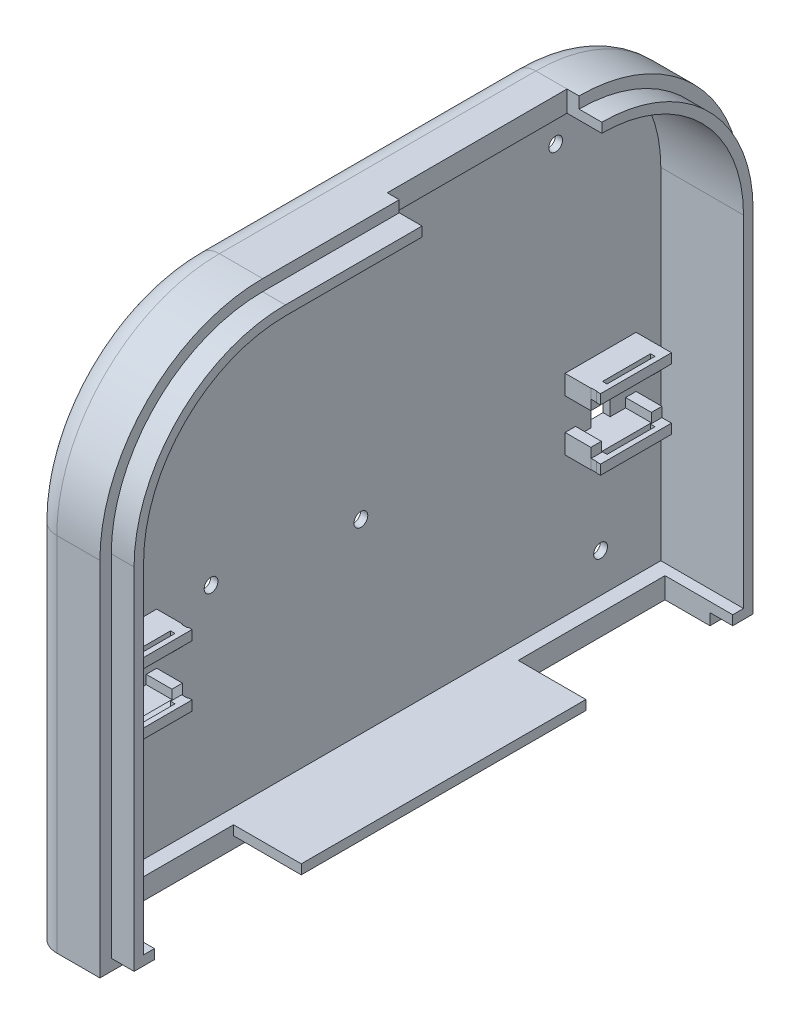
SolidWorks part; units mm, degrees
ref_plane "Front Plane" through (0, 0, 0) normal (0, 0, 1) x (1, 0, 0)
ref_plane "Top Plane" through (0, 0, 0) normal (0, 1, 0) x (1, 0, 0)
ref_plane "Right Plane" through (0, 0, 0) normal (1, 0, 0) x (0, 0, -1)
sketch "Sketch1" plane through (0, 0, 0) normal (1, 0, 0) x (0, 0, -1)
  line L0 (-52.8, 99.65) -> (52.8, 99.65)
  line L1 (-107.1, 45.35) -> (-107.1, -45.35)
  line L2 (-70, -75.35) -> (70, -75.35)
  line L3 (107.1, 45.35) -> (107.1, -45.35)
  line L4 (107.1, 0) -> (-107.1, 0) construction
  line L5 (0, 99.65) -> (0, -75.35) construction
  line L11 (107.1, -45.35) -> (107.1, -75.35)
  line L12 (107.1, -75.35) -> (70, -75.35)
  line L13 (-83.2, -1.7) -> (-76.8, -1.7)
  line L14 (-83.2, -1.7) -> (-83.2, -18.3)
  line L15 (-83.2, -18.3) -> (-76.8, -18.3)
  line L16 (-76.8, -1.7) -> (-76.8, -18.3)
  line L17 (-83.2, -1.7) -> (-76.8, -18.3) construction
  line L18 (-83.2, -18.3) -> (-76.8, -1.7) construction
  line L19 (76.8, -1.7) -> (83.2, -1.7)
  line L20 (76.8, -1.7) -> (76.8, -18.3)
  line L21 (76.8, -18.3) -> (83.2, -18.3)
  line L22 (83.2, -1.7) -> (83.2, -18.3)
  line L23 (76.8, -1.7) -> (83.2, -18.3) construction
  line L24 (76.8, -18.3) -> (83.2, -1.7) construction
  line L25 (80, -10) -> (-80, -10) construction
  line L27 (-107.1, -45.35) -> (-107.1, -75.35)
  line L28 (-107.1, -75.35) -> (-70, -75.35)
  arc A0 (52.8, 99.65) -> (107.1, 45.35) centre (52.8, 45.35) cw
  arc A1 (-52.8, 99.65) -> (-107.1, 45.35) centre (-52.8, 45.35) ccw
  point P16 (0, 0)
  point P17 (-80, -10)
  point P32 (80, -10)
  point P39 (-80, -10)
  point P40 (0, -10)
  dimension "D4" = 54.3
  dimension "D2" = 175
  dimension "D3" = 214.2
  dimension "D5" = 140
  dimension "D6" = 30
  dimension "D7" = 160
  dimension "D8" = 6.4
  dimension "D9" = 16.6
  dimension "D10" = 6.4
  dimension "D11" = 16.6
  dimension "D12" = 10
extrude "Boss-Extrude1" add sketch "Sketch1" along normal blind 2.4 contours L2 L3 A0 L0 A1 L1 L19 L22 L21 L20 L13 L16 L15 L14 region at (0, 9.6317, 0)
sketch "Sketch9" plane through (2.4, 0, 0) normal (1, 0, 0) x (0, 0, -1)
  line L17 (52.8, 99.65) -> (-52.8, 99.65)
  line L31 (52.8, 99.65) -> (-52.8, 99.65)
  line L32 (-107.1, 45.35) -> (-107.1, -75.35)
  line L33 (-107.1, 45.35) -> (-107.1, -75.35)
  line L34 (-107.1, -75.35) -> (107.1, -75.35)
  line L39 (107.1, -75.35) -> (107.1, 45.35)
  line L43 (107.1, -75.35) -> (107.1, 45.35)
  line L45 (-107.1, -75.35) -> (107.1, -75.35)
  arc A15 (-52.8, 99.65) -> (-107.1, 45.35) centre (-52.8, 45.35) ccw
  arc A16 (-52.8, 99.65) -> (-107.1, 45.35) centre (-52.8, 45.35) ccw
  arc A17 (107.1, 45.35) -> (52.8, 99.65) centre (52.8, 45.35) ccw
  arc A18 (107.1, 45.35) -> (52.8, 99.65) centre (52.8, 45.35) ccw
  dimension "D1" = 0
sketch "Sketch10" plane through (2.4, 0, 0) normal (1, 0, 0) x (0, 0, -1)
  line L0 (65, -55.35) -> (0, -55.35) construction
  line L1 (-65, -55.35) -> (65, -55.35) construction
  line L2 (-65, -55.35) -> (-65, 54.65) construction
  line L3 (-65, 54.65) -> (65, 54.65) construction
  line L4 (65, -55.35) -> (65, 54.65) construction
  line L5 (-65, -55.35) -> (65, 54.65) construction
  line L6 (-65, 54.65) -> (65, -55.35) construction
  line L7 (0, -55.35) -> (-65, -55.35) construction
  line L8 (-107.1, -75.35) -> (107.1, -75.35) construction
  line L9 (0, -0.35) -> (0, 0) construction
  line L10 (0, -0.35) -> (0, -6.35) construction
  circle A7 centre (-65, 54.65) radius 2.3
  circle A11 centre (0, -6.35) radius 2.3
  circle A12 centre (-50, -0.35) radius 2.3
  circle A13 centre (65, 69.65) radius 2.3
  circle A14 centre (80, -55.35) radius 2.3
  point P0 (0, -0.35)
  point P11 (0, -55.35)
  point P12 (32.5, -55.35)
  point P14 (-32.5, -55.35)
  point P18 (0, 0)
  dimension "D3" = 15
  dimension "D4" = 20
  dimension "D8" = 4.6
  dimension "D1" = 130
  dimension "D2" = 110
  dimension "D5" = 6
  dimension "D6" = 15
  dimension "D7" = 50
extrude "Cut-Extrude1" cut sketch "Sketch10" against normal blind 100 and the other way blind 1000
sketch "Sketch12" plane through (2.4, 0, 0) normal (1, 0, 0) x (0, 0, -1)
  line L5 (-88.35, -18.3) -> (-88.35, -15.3)
  line L6 (-88.35, -18.3) -> (-88.35, -1.7) construction
  line L22 (71.65, -18.3) -> (71.65, -15.3)
  line L23 (71.65, -18.3) -> (71.65, -1.7) construction
  line L24 (71.65, -18.3) -> (88.35, -18.3) construction
  line L25 (88.35, -18.3) -> (88.35, -1.7) construction
  line L26 (71.65, -1.7) -> (88.35, -1.7) construction
  line L27 (71.65, -18.3) -> (88.35, -1.7) construction
  line L28 (88.35, -18.3) -> (71.65, -1.7) construction
  line L29 (71.65, -1.7) -> (71.65, -4.7)
  line L30 (88.35, -18.3) -> (88.35, -15.3)
  line L31 (88.35, -1.7) -> (88.35, -4.7)
  line L32 (71.65, -1.7) -> (88.35, -1.7)
  line L33 (88.35, -18.3) -> (71.65, -18.3)
  line L34 (88.35, -15.3) -> (91.85, -15.3)
  line L35 (71.65, -15.3) -> (68.15, -15.3)
  line L36 (68.15, -15.3) -> (68.15, -21.8)
  line L37 (68.15, -21.8) -> (91.85, -21.8)
  line L38 (91.85, -21.8) -> (91.85, -15.3)
  line L39 (71.65, -4.7) -> (68.15, -4.7)
  line L40 (68.15, -4.7) -> (68.15, 1.8)
  line L41 (68.15, 1.8) -> (91.85, 1.8)
  line L42 (91.85, 1.8) -> (91.85, -4.7)
  line L43 (91.85, -4.7) -> (88.35, -4.7)
  line L44 (83.2, -18.3) -> (76.8, -1.7) construction
  line L45 (83.2, -1.7) -> (76.8, -18.3) construction
  line L46 (-88.35, -18.3) -> (-71.65, -18.3) construction
  line L47 (-71.65, -18.3) -> (-71.65, -1.7) construction
  line L48 (-88.35, -1.7) -> (-71.65, -1.7) construction
  line L49 (-88.35, -18.3) -> (-71.65, -1.7) construction
  line L50 (-71.65, -18.3) -> (-88.35, -1.7) construction
  line L51 (-88.35, -1.7) -> (-88.35, -4.7)
  line L52 (-71.65, -18.3) -> (-71.65, -15.3)
  line L53 (-71.65, -1.7) -> (-71.65, -4.7)
  line L54 (-88.35, -1.7) -> (-71.65, -1.7)
  line L55 (-71.65, -18.3) -> (-88.35, -18.3)
  line L56 (-71.65, -15.3) -> (-68.15, -15.3)
  line L57 (-88.35, -15.3) -> (-91.85, -15.3)
  line L58 (-91.85, -15.3) -> (-91.85, -21.8)
  line L59 (-91.85, -21.8) -> (-68.15, -21.8)
  line L60 (-68.15, -21.8) -> (-68.15, -15.3)
  line L61 (-88.35, -4.7) -> (-91.85, -4.7)
  line L62 (-91.85, -4.7) -> (-91.85, 1.8)
  line L63 (-91.85, 1.8) -> (-68.15, 1.8)
  line L64 (-68.15, 1.8) -> (-68.15, -4.7)
  line L65 (-68.15, -4.7) -> (-71.65, -4.7)
  line L66 (-76.8, -18.3) -> (-83.2, -1.7) construction
  line L67 (-83.2, -18.3) -> (-76.8, -1.7) construction
  point P3 (-0.1438, 64.1533)
  point P4 (-80, -10)
  point P19 (80, -10)
  point P21 (-80, -10)
  point P30 (380.6447, 32.9453)
  point P31 (130.7088, -20.4974)
  point P32 (80, -10)
  point P49 (169.9078, -49.5925)
  dimension "D3" = 16.7
  dimension "D4" = 16.6
  dimension "D5" = 10.6
  dimension "D6" = 3.5
  dimension "D7" = 3.5
  dimension "D8" = 3.5
  dimension "D9" = 3.5
  dimension "D10" = 4.9497
  dimension "D11" = 16.7
  dimension "D12" = 16.6
  dimension "D13" = 10.6
  dimension "D14" = 3.5
  dimension "D15" = 3.5
  dimension "D16" = 3.5
  dimension "D17" = 3.5
  dimension "D18" = 4.9497
  dimension "D19" = 4.9497
  dimension "D20" = 7.3824
  dimension "D21" = 23.5468
  dimension "D22" = 24.088
  dimension "D23" = 4.9497
  dimension "D24" = 7.3824
  dimension "D25" = 23.5468
  dimension "D26" = 24.088
extrude "Boss-Extrude2" add sketch "Sketch12" along normal blind 8.6
sketch "Sketch14" plane through (11, 0, 0) normal (1, 0, 0) x (0, 0, -1)
  line L0 (-91.85, 1.8) -> (-91.85, -4.7) construction
  line L1 (-91.85, 1.8) -> (-68.15, 1.8)
  line L2 (-91.85, 1.8) -> (-91.85, -1.45)
  line L3 (-91.85, -1.45) -> (-68.15, -1.45)
  line L4 (-68.15, 1.8) -> (-68.15, -1.45)
  line L5 (-68.15, 1.8) -> (-91.85, 1.8) construction
  line L6 (-68.15, -4.7) -> (-68.15, 1.8) construction
  line L7 (-68.15, -21.8) -> (-68.15, -15.3) construction
  line L8 (-91.85, -21.8) -> (-68.15, -21.8)
  line L9 (-91.85, -21.8) -> (-91.85, -18.55)
  line L10 (-91.85, -18.55) -> (-68.15, -18.55)
  line L11 (-68.15, -21.8) -> (-68.15, -18.55)
  line L12 (91.85, -21.8) -> (91.85, -15.3) construction
  line L13 (68.15, -21.8) -> (91.85, -21.8)
  line L14 (68.15, -21.8) -> (68.15, -18.55)
  line L15 (68.15, -18.55) -> (91.85, -18.55)
  line L16 (91.85, -21.8) -> (91.85, -18.55)
  line L17 (91.85, -4.7) -> (91.85, 1.8) construction
  line L18 (68.15, 1.8) -> (91.85, 1.8)
  line L19 (68.15, 1.8) -> (68.15, -1.45)
  line L20 (68.15, -1.45) -> (91.85, -1.45)
  line L21 (91.85, 1.8) -> (91.85, -1.45)
extrude "Boss-Extrude3" add sketch "Sketch14" along normal blind 3.2
sketch "Sketch16" plane through (0, -1.45, 0) normal (0, -1, 0) x (1, 0, 0)
  line L0 (11, 91.85) -> (11, 68.15) construction
  line L1 (11, 68.3952) -> (12.9651, 68.3952)
  line L2 (11, 68.3952) -> (11, 51.6632)
  line L3 (11, 51.6632) -> (12.9651, 51.6632)
  line L4 (12.9651, 68.3952) -> (12.9651, 51.6632)
  line L5 (11, -68.15) -> (11, -91.85) construction
  line L6 (11, -51.6659) -> (12.9651, -51.6659)
  line L7 (11, -51.6659) -> (11, -68.2634)
  line L8 (11, -68.2634) -> (12.9651, -68.2634)
  line L9 (12.9651, -51.6659) -> (12.9651, -68.2634)
extrude "Cut-Extrude2" cut sketch "Sketch16" against normal blind 100 and the other way blind 100
sketch "Sketch17" plane through (0, 0, 0) normal (1, 0, 0) x (0, 0, -1)
  line L0 (-103.9, 45.35) -> (-103.9, -72.15) construction
  line L1 (-103.9, -72.15) -> (103.9, -72.15) construction
  line L2 (103.9, -72.15) -> (103.9, 45.35) construction
  line L3 (52.8, 96.45) -> (-52.8, 96.45) construction
  line L4 (52.8, 99.65) -> (-52.8, 99.65)
  line L5 (-107.1, 45.35) -> (-107.1, -75.35)
  line L6 (-107.1, -75.35) -> (107.1, -75.35)
  line L7 (107.1, -75.35) -> (107.1, 45.35)
  line L8 (52.8, 99.65) -> (-52.8, 99.65) construction
  line L9 (-107.1, 45.35) -> (-107.1, -75.35) construction
  line L11 (107.1, -75.35) -> (107.1, 45.35) construction
  line L16 (100.1, -68.35) -> (100.1, 45.35)
  line L17 (52.8, 92.65) -> (-52.8, 92.65)
  line L18 (-100.1, 45.35) -> (-100.1, -68.35)
  line L19 (-100.1, -68.35) -> (100.1, -68.35)
  line L24 (52.8, 95.85) -> (-52.8, 95.85)
  line L25 (-103.3, 45.35) -> (-103.3, -71.55)
  line L27 (103.3, -71.55) -> (103.3, 45.35)
  line L28 (-107.1, -75.35) -> (107.1, -75.35) construction
  line L29 (-103.3, -71.55) -> (103.3, -71.55) construction
  line L31 (-103.3, -71.55) -> (103.3, -71.55)
  arc A0 (103.9, 45.35) -> (52.8, 96.45) centre (52.8, 45.35) ccw construction
  arc A1 (-52.8, 96.45) -> (-103.9, 45.35) centre (-52.8, 45.35) ccw construction
  arc A2 (-52.8, 99.65) -> (-107.1, 45.35) centre (-52.8, 45.35) ccw
  arc A3 (107.1, 45.35) -> (52.8, 99.65) centre (52.8, 45.35) ccw
  arc A4 (-52.8, 99.65) -> (-107.1, 45.35) centre (-52.8, 45.35) ccw construction
  arc A5 (107.1, 45.35) -> (52.8, 99.65) centre (52.8, 45.35) ccw construction
  arc A8 (100.1, 45.35) -> (52.8, 92.65) centre (52.8, 45.35) ccw
  arc A9 (-52.8, 92.65) -> (-100.1, 45.35) centre (-52.8, 45.35) ccw
  arc A12 (-52.8, 95.85) -> (-103.3, 45.35) centre (-52.8, 45.35) ccw
  arc A13 (103.3, 45.35) -> (52.8, 95.85) centre (52.8, 45.35) ccw
  dimension "D4" = 167.4
  dimension "D5" = 206.6
  dimension "D7" = 207.8
  dimension "D8" = 214.2
  dimension "D9" = 3.2
  dimension "D2" = 3.2
  dimension "D10" = 3.2
  dimension "D11" = 3.2
  dimension "D1" = 0
  dimension "D3" = 3.2
  dimension "D6" = 0.6
extrude "Boss-Extrude4" add sketch "Sketch17" along normal blind 30
sketch "Sketch21" plane through (2.4, 0, 0) normal (1, 0, 0) x (0, 0, -1)
  line L4 (-107.1, -75.35) -> (107.1, -75.35)
  line L6 (-107.1, -75.35) -> (107.1, -75.35)
  line L8 (52.8, 99.65) -> (-52.8, 99.65)
  line L9 (-107.1, 45.35) -> (-107.1, -75.35)
  line L11 (107.1, -75.35) -> (107.1, 45.35)
  line L12 (52.8, 99.65) -> (-52.8, 99.65)
  line L13 (-107.1, 45.35) -> (-107.1, -75.35)
  line L15 (107.1, -75.35) -> (107.1, 45.35)
  arc A4 (-52.8, 99.65) -> (-107.1, 45.35) centre (-52.8, 45.35) ccw
  arc A5 (107.1, 45.35) -> (52.8, 99.65) centre (52.8, 45.35) ccw
  arc A6 (-52.8, 99.65) -> (-107.1, 45.35) centre (-52.8, 45.35) ccw
  arc A7 (107.1, 45.35) -> (52.8, 99.65) centre (52.8, 45.35) ccw
  dimension "D1" = 0
sketch "Sketch22" plane through (2.4, 0, 0) normal (1, 0, 0) x (0, 0, -1)
  line L0 (-107.1, -75.35) -> (107.1, -75.35) construction
  line L1 (-107.1, -75.35) -> (107.1, -75.35)
  line L21 (52.8, 99.65) -> (-52.8, 99.65)
  line L22 (107.1, -75.35) -> (107.1, 45.35)
  line L24 (-107.1, 45.35) -> (-107.1, -75.35)
  line L25 (52.8, 99.65) -> (-52.8, 99.65)
  line L26 (107.1, -75.35) -> (107.1, 45.35)
  line L28 (-107.1, 45.35) -> (-107.1, -75.35)
  line L44 (-103.3, -71.55) -> (103.3, -71.55)
  line L45 (103.3, -71.55) -> (103.3, 45.35)
  line L46 (52.8, 95.85) -> (-52.8, 95.85)
  line L47 (-103.3, 45.35) -> (-103.3, -71.55)
  line L48 (-103.3, -71.55) -> (103.3, -71.55)
  line L49 (103.3, -71.55) -> (103.3, 45.35)
  line L50 (52.8, 95.85) -> (-52.8, 95.85)
  line L51 (-103.3, 45.35) -> (-103.3, -71.55)
  arc A6 (-52.8, 99.65) -> (-107.1, 45.35) centre (-52.8, 45.35) ccw
  arc A7 (107.1, 45.35) -> (52.8, 99.65) centre (52.8, 45.35) ccw
  arc A8 (-52.8, 99.65) -> (-107.1, 45.35) centre (-52.8, 45.35) ccw
  arc A9 (107.1, 45.35) -> (52.8, 99.65) centre (52.8, 45.35) ccw
  arc A20 (103.3, 45.35) -> (52.8, 95.85) centre (52.8, 45.35) ccw
  arc A21 (-52.8, 95.85) -> (-103.3, 45.35) centre (-52.8, 45.35) ccw
  arc A22 (103.3, 45.35) -> (52.8, 95.85) centre (52.8, 45.35) ccw
  arc A23 (-52.8, 95.85) -> (-103.3, 45.35) centre (-52.8, 45.35) ccw
  dimension "D1" = 0
  dimension "D2" = 0
extrude "Boss-Extrude7" add sketch "Sketch22" along normal blind 20
sketch "Sketch23" plane through (0, -75.35, 0) normal (0, -1, 0) x (1, 0, 0)
  line L0 (0, 99.1) -> (0, 107.1)
  line L1 (0, 107.1) -> (8, 107.1)
  line L2 (8, -107.1) -> (0, -107.1)
  line L3 (0, -107.1) -> (0, -99.1)
  line L8 (0, 107.1) -> (0, -107.1)
  line L9 (0, -107.1) -> (22.4, -107.1)
  line L10 (22.4, -107.1) -> (22.4, 107.1)
  line L11 (22.4, 107.1) -> (0, 107.1)
  line L12 (0, 99.1) -> (0, -99.1) construction
  line L13 (8, -107.1) -> (22.4, -107.1) construction
  line L15 (22.4, 107.1) -> (8, 107.1) construction
  arc A0 (0, 99.1) -> (8, 107.1) centre (8, 99.1) cw
  arc A1 (0, -99.1) -> (8, -107.1) centre (8, -99.1) ccw
  dimension "D2" = 8
  dimension "D1" = 0
extrude "Cut-Extrude4" cut sketch "Sketch23" against normal through all
fillet "Fillet4" radius 8 5 edges at (0, 92.7258, 79.3335) (0, 99.65, 0) (0, 92.7258, -79.3335) (1.5353, 63.957, 103.8124) (1.5353, 63.957, -103.8124)
sketch "Sketch26" plane through (22.4, 0, 0) normal (1, 0, 0) x (0, 0, -1)
  line L1 (-47.5, -68.3365) -> (47.5, -68.3365)
  line L2 (47.5, -68.3365) -> (47.5, -71.55)
  line L6 (47.5, -71.55) -> (-47.5, -71.55)
  line L7 (-47.5, -71.55) -> (-47.5, -68.3365)
  line L8 (-103.3, -71.55) -> (103.3, -71.55) construction
  line L9 (-96.5, -79.5369) -> (96.5, -79.5369)
  line L10 (-96.5, -79.5369) -> (-96.5, -63.5631)
  line L11 (-96.5, -63.5631) -> (96.5, -63.5631)
  line L12 (96.5, -79.5369) -> (96.5, -63.5631)
  line L13 (-96.5, -79.5369) -> (96.5, -63.5631) construction
  line L14 (-96.5, -63.5631) -> (96.5, -79.5369) construction
  line L15 (107.1, -75.35) -> (107.1, 45.35) construction
  point P0 (0, -71.55)
  point P9 (0, -68.3365)
  point P13 (0, -68.3365)
  point P16 (0, -68.3365)
  dimension "D1" = 10.6
  dimension "D2" = 15.9739
  dimension "D3" = 95
  dimension "D4" = 3.2135
extrude "Cut-Extrude7" cut sketch "Sketch26" against normal blind 15 and the other way blind 20
sketch "Sketch28" plane through (0, 99.65, 0) normal (0, 1, 0) x (1, 0, 0)
  line L0 (22.4, 52.8) -> (18.4, 52.8)
  line L1 (22.4, 52.8) -> (8, 52.8) construction
  line L2 (18.4, 52.8) -> (18.4, -7.2)
  line L3 (18.4, -7.2) -> (53.1003, -7.2)
  line L4 (53.1003, -7.2) -> (53.1003, 52.8)
  line L5 (53.1003, 52.8) -> (22.4, 52.8)
  dimension "D1" = 4
  dimension "D2" = 60
extrude "Cut-Extrude8" cut sketch "Sketch28" against normal blind 10
sketch "Sketch29" plane through (0, -1.45, 0) normal (0, -1, 0) x (1, 0, 0)
  line L5 (11, 91.85) -> (11, 68.3952) construction
  line L7 (11, 88.1226) -> (11, 72.1226)
  line L8 (11, 72.1226) -> (12.5, 72.1226)
  line L9 (12.5, 72.1226) -> (12.5, 88.1226)
  line L10 (12.5, 88.1226) -> (11, 88.1226)
  line L12 (11, -68.2634) -> (11, -91.85) construction
  line L13 (11, -72.0567) -> (11, -88.0567)
  line L14 (11, -88.0567) -> (12.5, -88.0567)
  line L15 (12.5, -88.0567) -> (12.5, -72.0567)
  line L16 (12.5, -72.0567) -> (11, -72.0567)
  point P0 (11, 80.1226)
  point P1 (11, -80.0567)
  point P6 (11, 80.1226)
  point P9 (11, -80.0567)
  point P14 (11, -80.0567)
  dimension "D1" = 16
  dimension "D2" = 1.5
  dimension "D3" = 16
  dimension "D4" = 1.5
extrude "Cut-Extrude9" cut sketch "Sketch29" against normal blind 30 and the other way blind 1000
